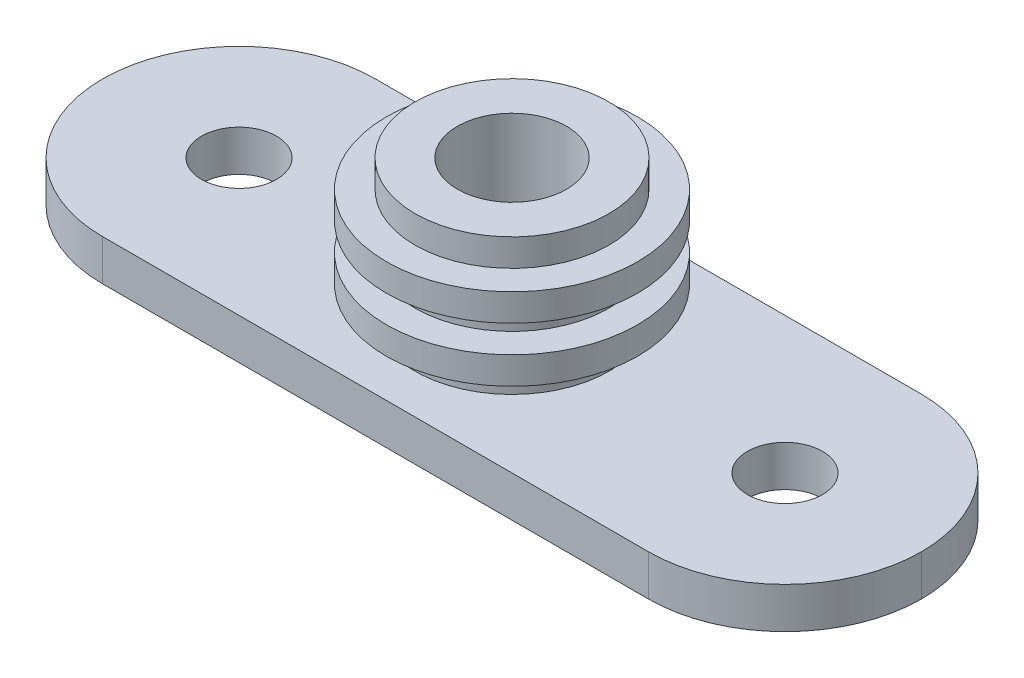
SolidWorks part; units mm, degrees
ref_plane "Front Plane" through (0, 0, 0) normal (0, 0, 1) x (1, 0, 0)
ref_plane "Top Plane" through (0, 0, 0) normal (0, 1, 0) x (1, 0, 0)
ref_plane "Right Plane" through (0, 0, 0) normal (1, 0, 0) x (0, 0, -1)
sketch "Sketch1" plane through (0, 0, 0) normal (0, 1, 0) x (1, 0, 0)
  line L1 (-30, -10) -> (30, -10)
  line L2 (-30, -10) -> (-30, 10)
  line L3 (-30, 10) -> (30, 10)
  line L4 (30, -10) -> (30, 10)
  line L5 (-30, -10) -> (30, 10) construction
  line L6 (-30, 10) -> (30, -10) construction
  point P0 (0, 0)
  dimension "D1" = 20
  dimension "D2" = 60
extrude "Boss-Extrude1" add sketch "Sketch1" along normal blind 3
fillet "Fillet1" radius 10 4 edges at (30, 1.5, -10) (30, 1.5, 10) (-30, 1.5, 10) (-30, 1.5, -10)
sketch "Sketch36" plane through (0, 3, 0) normal (0, 1, 0) x (1, 0, 0)
  circle A0 centre (0, 0) radius 7.1
  dimension "D1" = 14.2
extrude "Boss-Extrude15" add sketch "Sketch36" along normal blind 2
sketch "Sketch37" plane through (0, 5, 0) normal (0, 1, 0) x (1, 0, 0)
  circle A0 centre (0, 0) radius 9.2
  dimension "D1" = 18.4
extrude "Boss-Extrude16" add sketch "Sketch37" along normal blind 2
sketch "Sketch39" plane through (0, 7, 0) normal (0, 1, 0) x (1, 0, 0)
  circle A0 centre (0, 0) radius 7.1
  dimension "D1" = 14.2
extrude "Boss-Extrude18" add sketch "Sketch39" along normal blind 2
sketch "Sketch40" plane through (0, 9, 0) normal (0, 1, 0) x (1, 0, 0)
  circle A0 centre (0, 0) radius 9.2
  dimension "D1" = 18.4
extrude "Boss-Extrude19" add sketch "Sketch40" along normal blind 2
sketch "Sketch41" plane through (0, 11, 0) normal (0, 1, 0) x (1, 0, 0)
  circle A0 centre (0, 0) radius 7.1
  dimension "D1" = 14.2
extrude "Boss-Extrude20" add sketch "Sketch41" along normal blind 2
sketch "Sketch42" plane through (0, 13, 0) normal (0, 1, 0) x (1, 0, 0)
  circle A0 centre (0, 0) radius 4
  dimension "D1" = 8
extrude "Cut-Extrude5" cut sketch "Sketch42" against normal up to surface (13 mm away) up to face at (0, 0, 0)
sketch "Sketch43" plane through (0, 3, 0) normal (0, 1, 0) x (1, 0, 0)
  line L0 (-20, 0) -> (20, 0) construction
  circle A0 centre (-20, 0) radius 2.75
  circle A1 centre (20, 0) radius 2.75
  point P7 (0, 0)
  dimension "D2" = 5.5
  dimension "D3" = 5.5
  dimension "D1" = 40
extrude "Cut-Extrude6" cut sketch "Sketch43" against normal up to surface (3 mm away) up to face at (0, 0, -4)
